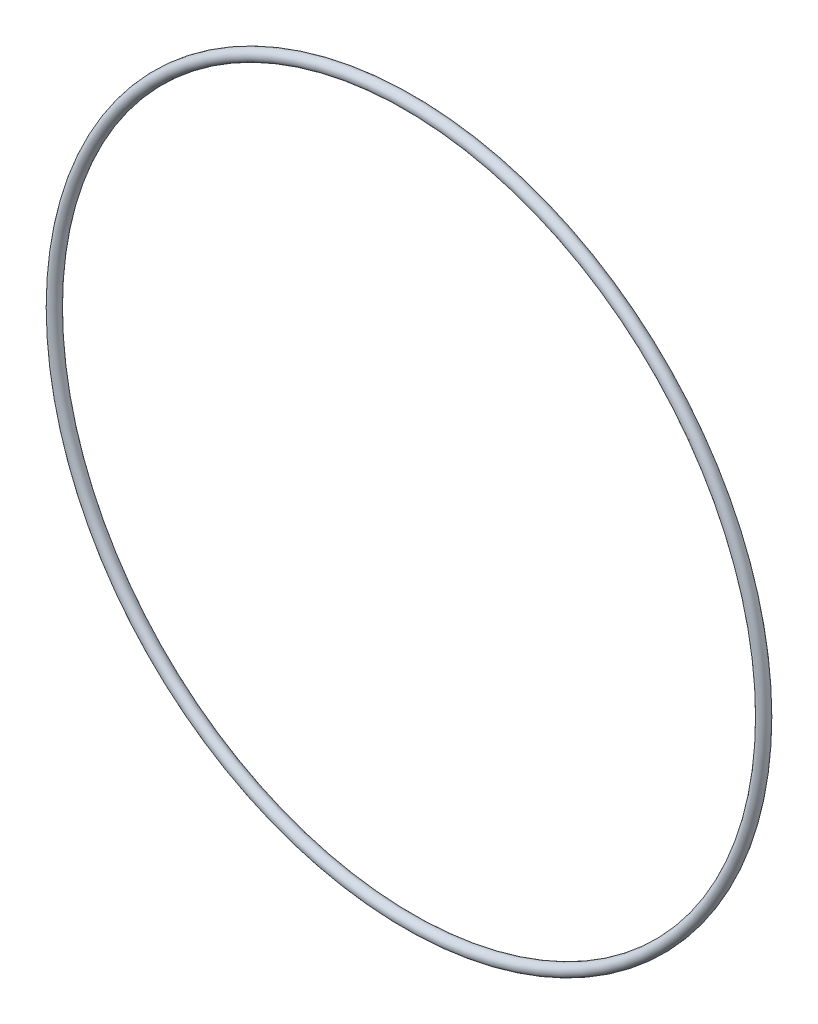
SolidWorks part; units mm, degrees
ref_plane "Front" through (0, 0, 0) normal (0, 0, 1) x (1, 0, 0)
ref_plane "Top" through (0, 0, 0) normal (0, 1, 0) x (1, 0, 0)
ref_plane "Right" through (0, 0, 0) normal (1, 0, 0) x (0, 0, -1)
sketch "Sketch1" plane through (0, 0, 0) normal (1, 0, 0) x (0, -1, 0)
  line L0 (0, -0.889) -> (0, 0.889) construction
  line L2 (-61.1746, 0) -> (61.1746, 0) construction
  line L3 (-53.8353, 0) -> (53.8353, 0) construction
  circle A0 centre (54.7243, 0) radius 0.889
  point P9 (53.8353, 0)
  point P10 (55.6133, 0)
  point P13 (54.7243, 0.889)
  point P14 (54.7243, -0.889)
  dimension "Width" = 1.778
  dimension "ID" = 107.6706
revolve "Revolve1" add sketch "Sketch1" angle 360 about L0
ref_axis "Axis1" through (0, 0, -0.9779) along (0, 0, 1)
